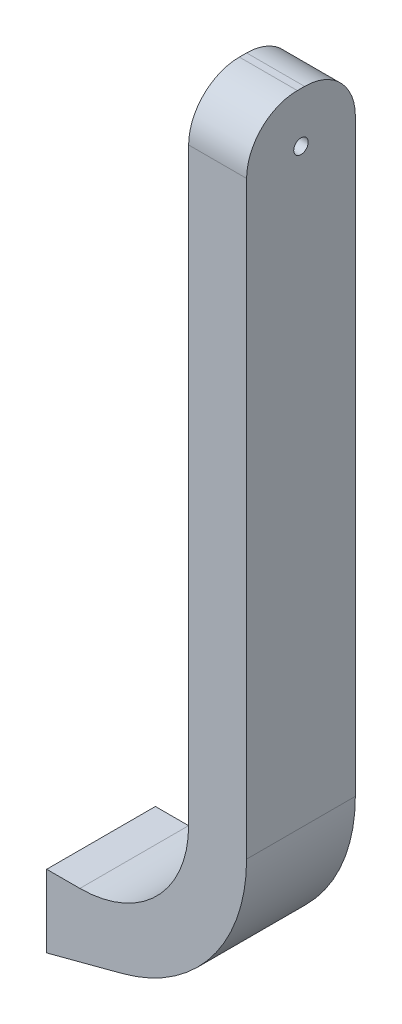
SolidWorks part; units mm, degrees
ref_plane "Front Plane" through (0, 0, 0) normal (0, 0, 1) x (1, 0, 0)
ref_plane "Top Plane" through (0, 0, 0) normal (0, 1, 0) x (1, 0, 0)
ref_plane "Right Plane" through (0, 0, 0) normal (1, 0, 0) x (0, 0, -1)
sketch "Sketch1" plane through (0, 0, 0) normal (0, 0, 1) x (1, 0, 0)
  line L0 (96.8142, 422.2536) -> (101.3962, 422.2536)
  line L1 (116.3962, 437.2536) -> (116.3962, 525.5762)
  line L9 (124.3962, 437.2536) -> (124.3962, 525.5762)
  line L10 (124.3962, 525.5762) -> (116.3962, 525.5762)
  line L11 (96.8142, 422.2536) -> (96.8142, 412.2536)
  line L12 (96.8142, 412.2536) -> (107.2717, 415.0168)
  line L14 (96.8142, 414.2536) -> (101.3962, 414.2536) construction
  arc A1 (101.3962, 422.2536) -> (116.3962, 437.2536) centre (101.3962, 437.2536) ccw
  arc A3 (107.2717, 415.0168) -> (124.3962, 437.2536) centre (101.3962, 437.2536) ccw
  arc A4 (101.3962, 414.2536) -> (124.3962, 437.2536) centre (101.3962, 437.2536) ccw construction
  point P9 (0, 0)
  point P11 (96.8142, 414.2536)
  point P12 (96.8142, 414.2536)
  point P13 (0, 0)
  point P14 (0, 0)
  dimension "D1" = 8
extrude "Boss-Extrude1" add sketch "Sketch1" against normal up to surface (15 mm away)
fillet "Fillet1" radius 7 2 edges at (120.3962, 525.5762, -15) (120.3962, 525.5762, 0)
sketch "Sketch2" plane through (116.3962, 0, 0) normal (-1, 0, 0) x (0, 0, 1)
  circle A0 centre (-7.5, 518.6762) radius 1
extrude "Cut-Extrude1" cut sketch "Sketch2" against normal up to surface (8 mm away) up to face at (124.3962, 494.2853, -7.5)
